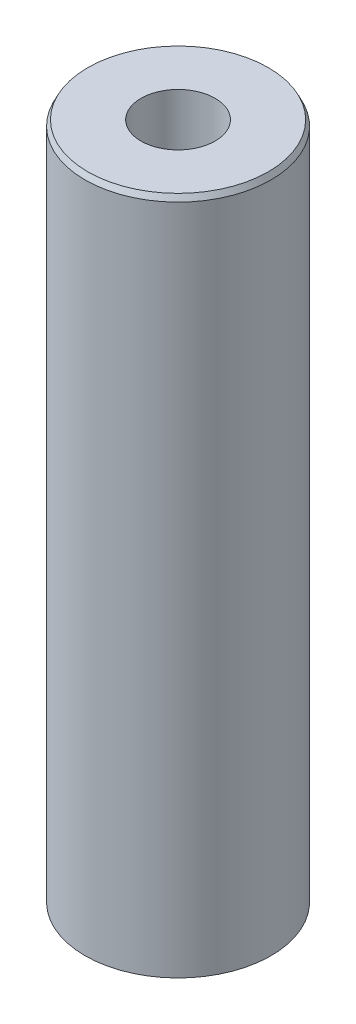
SolidWorks part; units mm, degrees
ref_plane "Front Plane" through (0, 0, 0) normal (0, 0, 1) x (1, 0, 0)
ref_plane "Top Plane" through (0, 0, 0) normal (0, 1, 0) x (1, 0, 0)
ref_plane "Right Plane" through (0, 0, 0) normal (1, 0, 0) x (0, 0, -1)
sketch "Sketch1" plane through (0, 0, 0) normal (0, 1, 0) x (1, 0, 0)
  circle A0 centre (0, 0) radius 55
  dimension "SHAFT_OD" = 110
extrude "Boss-Extrude1" add sketch "Sketch1" along normal blind 402.265
sketch "Sketch2" plane through (0, 0, 0) normal (0, 1, 0) x (1, 0, 0)
  circle A0 centre (0, 0) radius 21.9276
  dimension "BORE_D" = 43.8552
extrude "Cut-Extrude1" cut sketch "Sketch2" along normal through all
chamfer "Chamfer1" distance 3.3419 angle 26.04 2 edges at (0, 402.265, 55) (0, 0, 55) first distance on face at (0, 402.265, 55) first distance on face at (0, 0, 21.9276)
